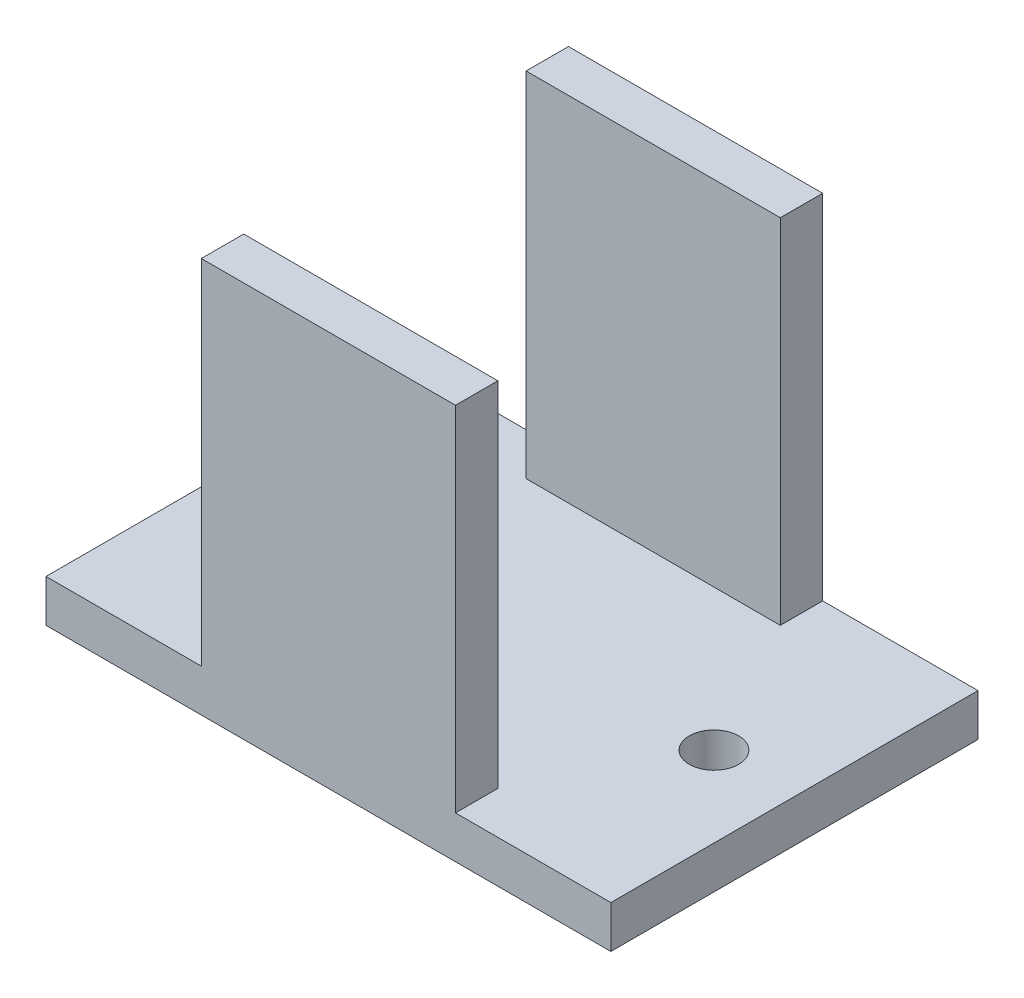
SolidWorks part; units mm, degrees
ref_plane "Front Plane" through (0, 0, 0) normal (0, 0, 1) x (1, 0, 0)
ref_plane "Top Plane" through (0, 0, 0) normal (0, 1, 0) x (1, 0, 0)
ref_plane "Right Plane" through (0, 0, 0) normal (1, 0, 0) x (0, 0, -1)
sketch "Sketch1" plane through (0, 0, 0) normal (0, 1, 0) x (1, 0, 0)
  line L1 (-20, 13) -> (20, 13)
  line L2 (-20, 13) -> (-20, -13)
  line L3 (-20, -13) -> (20, -13)
  line L4 (20, 13) -> (20, -13)
  point P5 (0, 0)
  point P7 (0, 0)
  dimension "D1" = 40
  dimension "D2" = 26
  dimension "D3" = 13
  dimension "D4" = 20
extrude "Boss-Extrude1" add sketch "Sketch1" along normal blind 3 contours L1 L4 L3 L2
sketch "Sketch2" plane through (0, 3, 0) normal (0, 1, 0) x (1, 0, 0)
  line L0 (20, 0) -> (14.3, 0) construction
  line L1 (20, 13) -> (20, -13) construction
  line L2 (0, 13) -> (0, -13) construction
  line L3 (-20, 13) -> (20, 13) construction
  line L4 (-20, -13) -> (20, -13) construction
  line L5 (-20, 0) -> (-14.3, 0) construction
  circle A0 centre (14.3, 0) radius 1.75
  circle A1 centre (-14.3, 0) radius 1.75
extrude "Cut-Extrude1" cut sketch "Sketch2" against normal blind 3
sketch "Sketch3" plane through (0, 3, 0) normal (0, 1, 0) x (1, 0, 0)
  line L0 (-20, 13) -> (20, 13) construction
  line L1 (0, 0) -> (50000, 0) construction
  line L2 (0, 0) -> (0, 50000) construction
  line L3 (-9, -10) -> (9, -10)
  line L4 (-9, 13) -> (9, 13)
  line L5 (-9, 13) -> (-9, 10)
  line L6 (-9, 10) -> (9, 10)
  line L7 (9, 13) -> (9, 10)
  line L8 (9, -13) -> (9, -10)
  line L9 (-9, -13) -> (9, -13)
  line L10 (-9, -13) -> (-9, -10)
  point P0 (-9, 13)
  point P9 (9, 13)
  dimension "D1" = 11
  dimension "D2" = 3
extrude "Boss-Extrude2" add sketch "Sketch3" along normal blind 25
